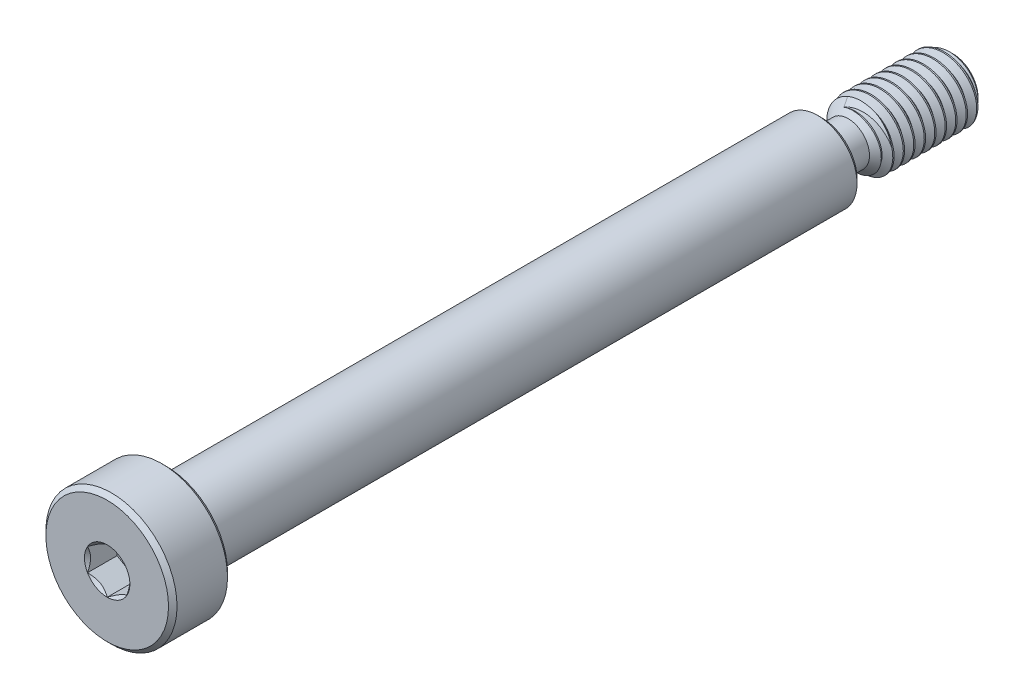
SolidWorks part; units mm, degrees
ref_plane "Front Plane" through (0, 0, 0) normal (0, 0, 1) x (1, 0, 0)
ref_plane "Top Plane" through (0, 0, 0) normal (0, 1, 0) x (1, 0, 0)
ref_plane "Right Plane" through (0, 0, 0) normal (1, 0, 0) x (0, 0, -1)
sketch "Sketch1" plane through (0, 0, 0) normal (1, 0, 0) x (0, 0, -1)
  line L0 (-32.25, 0) -> (32.25, 0) construction
  line L1 (-32.25, -5) -> (-32.25, 5) construction
  line L2 (-32.25, 5) -> (-27.75, 5) construction
  line L3 (-27.75, 5) -> (-27.75, 2.797) construction
  line L4 (-27.75, 2.797) -> (-27.242, 2.797) construction
  line L5 (-27.242, 2.797) -> (-27.039, 3) construction
  line L6 (-27.039, 3) -> (22.25, 3) construction
  line L7 (32.2, 2.5866) -> (32.6, 1.8938) construction
  line L8 (32.6, 1.8938) -> (33, 2.5866) construction
  line L9 (32.25, -2.5) -> (32.25, 2.5) construction
  line L10 (22.25, 3) -> (32.25, 3) construction
  line L11 (33, 2.5866) -> (32.2, 2.5866) construction
  line L12 (32.6, 2.5866) -> (32.6, 2.5) construction
  line L13 (32.6, 1.8938) -> (32.6, 1.9804) construction
  line L14 (32.65, 1.9804) -> (32.55, 1.9804) construction
  line L15 (32.95, 2.5) -> (32.25, 2.5) construction
  line L16 (32.6, 2.5433) -> (32.975, 2.5433) construction
  line L17 (32.6, 2.5433) -> (32.225, 2.5433) construction
  line L18 (-32.25, 4.675) -> (-31.925, 5) construction
  line L19 (-28.075, 5) -> (-27.75, 4.675) construction
  line L20 (32.25, 2.5) -> (22.25, 2.5) construction
  line L21 (31.65, 2.5) -> (32.25, 1.9) construction
  line L22 (25.125, 2.5) -> (24.25, 1.625) construction
  line L23 (24.25, 1.625) -> (22.6875, 1.625) construction
  line L24 (22.25, 2.5) -> (22.25, 2.0625) construction
  line L25 (-30, 1.5) -> (-30, -1.5) construction
  line L26 (-30, -1.5) -> (-32.25, -1.5) construction
  line L27 (-30, 1.5) -> (-32.25, 1.5) construction
  line L28 (-31.8288, 0) -> (-28.1713, 0) construction
  arc A0 (22.25, 2.0625) -> (22.6875, 1.625) centre (22.6875, 2.0625) ccw construction
  point P4 (0, 0)
  point P7 (-32.25, 0)
  point P18 (32.25, 0)
  point P25 (29.45, -2.5)
  point P38 (-30, 5)
  point P45 (-30, 0)
  point P46 (24.6875, 2.0625)
  point P48 (-27.242, 0)
  point P51 (-30, 0)
  point P52 (22.25, 0)
  point P53 (-25.9424, 0)
  dimension "Head Diameter" = 10
  dimension "Head Height" = 4.5
  dimension "Thread Diameter" = 5
  dimension "Shoulder Diameter" = 6
  dimension "Thread Length" = 10
  dimension "D1" = 0.508
  dimension "D2" = 135
  dimension "D3" = 0.203
  dimension "Shoulder Length" = 50
  dimension "Thread Pitch" = 0.8
  dimension "D4" = 0.1
  dimension "D5" = 2.8
  dimension "D6" = 0.325
  dimension "D7" = 0.6
  dimension "D8" = 3.25
  dimension "D9" = 2
  dimension "Drive Size" = 3
  dimension "D10" = 3.85
  dimension "D11" = 3.6575
  dimension "D12" = 6.3076
sketch "Sketch3" plane through (0, 0, 0) normal (1, 0, 0) x (0, 0, -1)
  line L0 (-32.25, 0) -> (-32.25, 4.675)
  line L1 (-32.25, -5) -> (-32.25, 5) construction
  line L2 (-32.25, 4.675) -> (-31.925, 5)
  line L3 (-31.925, 5) -> (-28.075, 5)
  line L4 (-28.075, 5) -> (-27.75, 4.675)
  line L5 (-27.75, 4.675) -> (-27.75, 2.797)
  line L6 (-27.75, 2.797) -> (-27.242, 2.797)
  line L7 (-27.242, 2.797) -> (-27.039, 3)
  line L8 (-27.039, 3) -> (22.25, 3)
  line L9 (22.25, 3) -> (22.25, 2.0625)
  line L10 (22.6875, 1.625) -> (24.25, 1.625)
  line L11 (24.25, 1.625) -> (25.125, 2.5)
  line L12 (25.125, 2.5) -> (31.65, 2.5)
  line L13 (31.65, 2.5) -> (32.25, 1.9)
  line L14 (32.25, 1.9) -> (32.25, 0)
  line L15 (32.25, 0) -> (-32.25, 0)
  arc A0 (22.25, 2.0625) -> (22.6875, 1.625) centre (22.6875, 2.0625) ccw construction
  arc A1 (22.25, 2.0625) -> (22.6875, 1.625) centre (22.6875, 2.0625) ccw
revolve "Revolve1" add sketch "Sketch3" angle 360 about L0
sketch "Sketch4" plane through (0, 0, 0) normal (0, 0, 1) x (1, 0, 0)
  line L0 (0, -5) -> (0, 5) construction
  line L1 (0, 1.7321) -> (-1.5, 0.866)
  line L2 (-1.5, 0.866) -> (-1.5, -0.866)
  line L3 (-1.5, -0.866) -> (0, -1.7321)
  line L4 (0, -1.7321) -> (1.5, -0.866)
  line L5 (1.5, -0.866) -> (1.5, 0.866)
  line L6 (1.5, 0.866) -> (0, 1.7321)
  circle A0 centre (0, 0) radius 1.5 construction
extrude "Cut-Extrude1" cut sketch "Sketch4" against normal up to vertex (-30 mm away) from vertex up to point (0, 0, 30) starting at point (0, 0, 32.25)
sketch "Sketch5" plane through (0, 0, 0) normal (0, 0, 1) x (1, 0, 0)
  line L0 (0, -5) -> (0, 5) construction
  circle A0 centre (0, 0) radius 1.7321
extrude "Cut-Extrude2" cut sketch "Sketch5" against normal up to vertex (-30 mm away) draft 45 from vertex up to point (0, 0, 30) starting at point (0, 0, 32.25)
chamfer "Chamfer1" distance 0.325 angle 45 1 edges at (3, 0, -22.25)
sketch "Sketch6" plane through (0, 0, -32.25) normal (0, 0, -1) x (-1, 0, 0)
  circle A0 centre (0, 0) radius 2.5
curve "Helix/Spiral1" pitch 0.8 height 9.5 radius 2.5 centre (0, 0, -32.25) axis (0, 0, 1) start towards (0, 1, 0)
sketch "Sketch7" plane through (0, 0, 0) normal (1, 0, 0) x (0, 0, -1)
  line L0 (32.225, 2.5433) -> (32.55, 1.9804)
  line L1 (32.55, 1.9804) -> (32.65, 1.9804)
  line L2 (32.65, 1.9804) -> (32.975, 2.5433)
  line L3 (32.975, 2.5433) -> (32.225, 2.5433)
sweep "Cut-Sweep1" cut profiles "Sketch7" path "Helix/Spiral1"
equation "\"D4@Sketch1\"=\"Thread Pitch@Sketch1\"/8"
equation "\"D5@Sketch1\"=\"Thread Pitch@Sketch1\"*3.5"
equation "\"D6@Sketch1\"=\"Head Diameter@Sketch1\"*.0325"
equation "\"D7@Sketch1\"=\"Thread Pitch@Sketch1\"*.75"
equation "\"D8@Sketch1\"=\"Thread Diameter@Sketch1\"*.65"
equation "\"D9@Sketch1\"=\"Thread Length@Sketch1\"*.2"
equation "\"D1@Chamfer1\"=\"D6@Sketch1\""
equation "\"D4@Helix/Spiral1\"=\"Thread Pitch@Sketch1\""
equation "\"D3@Helix/Spiral1\"=\"Thread Length@Sketch1\"*.95"
